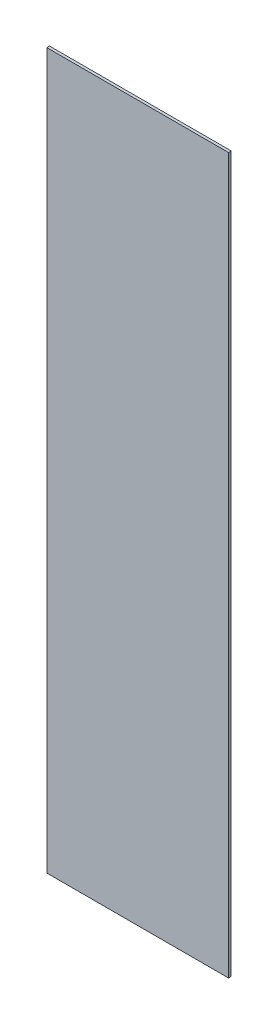
SolidWorks part; units mm, degrees
material "1060 Alloy"
ref_plane "Front Plane" through (0, 0, 0) normal (0, 0, 1) x (1, 0, 0)
ref_plane "Top Plane" through (0, 0, 0) normal (0, 1, 0) x (1, 0, 0)
ref_plane "Right Plane" through (0, 0, 0) normal (1, 0, 0) x (0, 0, -1)
sketch "Sketch1" plane through (0, 0, 0) normal (0, 0, 1) x (1, 0, 0)
  line L1 (-77.5, 304.8) -> (77.5, 304.8)
  line L2 (-77.5, 304.8) -> (-77.5, -304.8)
  line L3 (-77.5, -304.8) -> (77.5, -304.8)
  line L4 (77.5, 304.8) -> (77.5, -304.8)
  line L5 (-77.5, 304.8) -> (77.5, -304.8) construction
  line L6 (-77.5, -304.8) -> (77.5, 304.8) construction
  point P0 (0, 0)
  point P5 (69.5, 244.8)
  point P7 (69.5, 228.8)
  point P8 (69.5, 236.8)
  point P9 (69.5, 220.8)
  point P10 (69.5, 212.8)
  point P11 (69.5, 8)
  point P12 (69.5, 16)
  point P13 (69.5, -212.8)
  point P14 (69.5, -228.8)
  point P15 (69.5, -220.8)
  point P16 (69.5, -236.8)
  point P17 (69.5, -244.8)
  point P18 (69.5, -8)
  point P19 (69.5, -16)
  point P22 (69.5, 0)
  dimension "D1" = 609.6
  dimension "D2" = 155
  dimension "D3" = 8
  dimension "D4" = 60
  dimension "D5" = 8
  dimension "D6" = 8
  dimension "D7" = 8
  dimension "D8" = 8
  dimension "D9" = 60
  dimension "D10" = 8
  dimension "D11" = 8
  dimension "D12" = 8
  dimension "D13" = 8
  dimension "D14" = 8
  dimension "D15" = 8
  dimension "D16" = 8
  dimension "D17" = 8
  dimension "D18" = 8
  dimension "D19" = 8
extrude "Boss-Extrude1" add sketch "Sketch1" along normal blind 2.305
